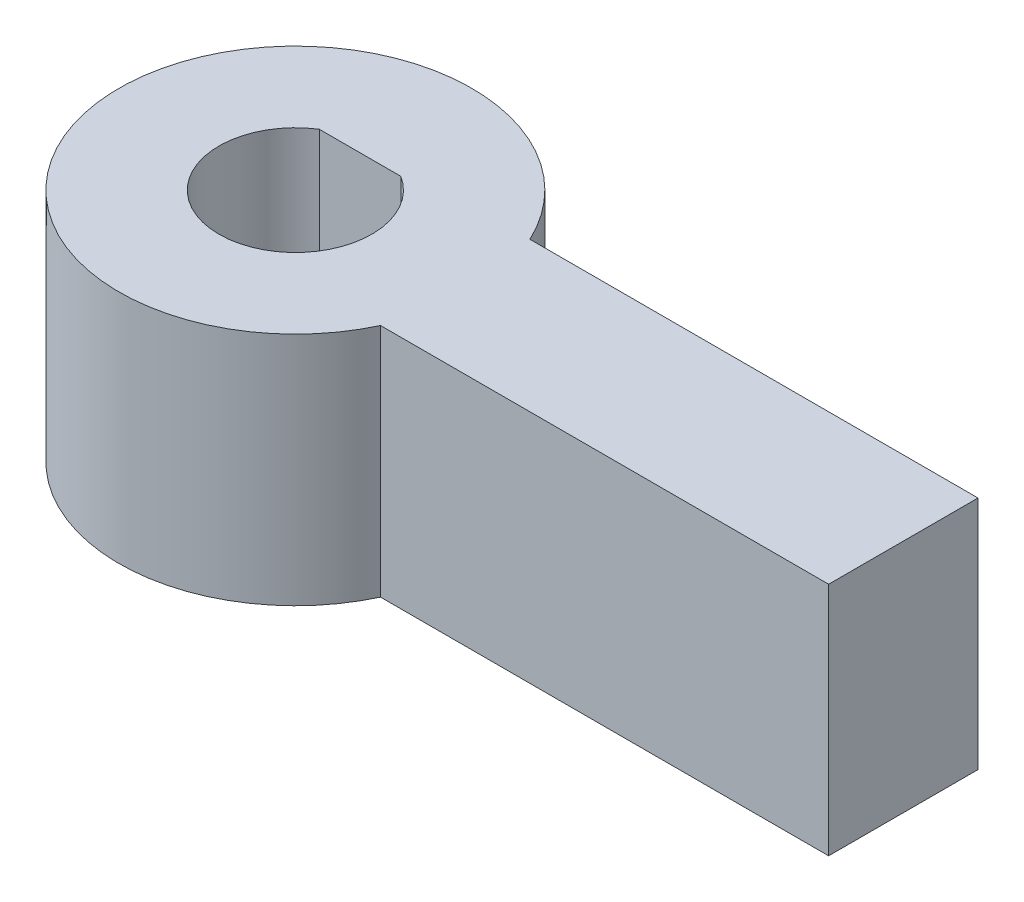
SolidWorks part; units mm, degrees
ref_plane "Front Plane" through (0, 0, 0) normal (0, 0, 1) x (1, 0, 0)
ref_plane "Top Plane" through (0, 0, 0) normal (0, 1, 0) x (1, 0, 0)
ref_plane "Right Plane" through (0, 0, 0) normal (1, 0, 0) x (0, 0, -1)
sketch "Sketch1" plane through (0, 0, 0) normal (0, 1, 0) x (1, 0, 0)
  line L0 (1.6583, 2.5) -> (-1.6583, 2.5) construction
  line L1 (1.7321, 2.75) -> (-1.7321, 2.75)
  line L3 (6.7948, 3.175) -> (25.8448, 3.175)
  line L4 (25.8448, 3.175) -> (25.8448, -3.175)
  line L5 (25.8448, -3.175) -> (6.7948, -3.175)
  arc A0 (-1.6583, 2.5) -> (1.6583, 2.5) centre (0, 0) ccw construction
  arc A1 (-1.7321, 2.75) -> (1.7321, 2.75) centre (0, 0) ccw
  arc A2 (6.7948, 3.175) -> (6.7948, -3.175) centre (0, 0) ccw
  dimension "D1" = 6
  dimension "D4" = 15
  dimension "D2" = 2.5
  dimension "D5" = 6.35
  dimension "D6" = 19.05
  dimension "D3" = 0.25
extrude "Boss-Extrude1" add sketch "Sketch1" along normal blind 10
